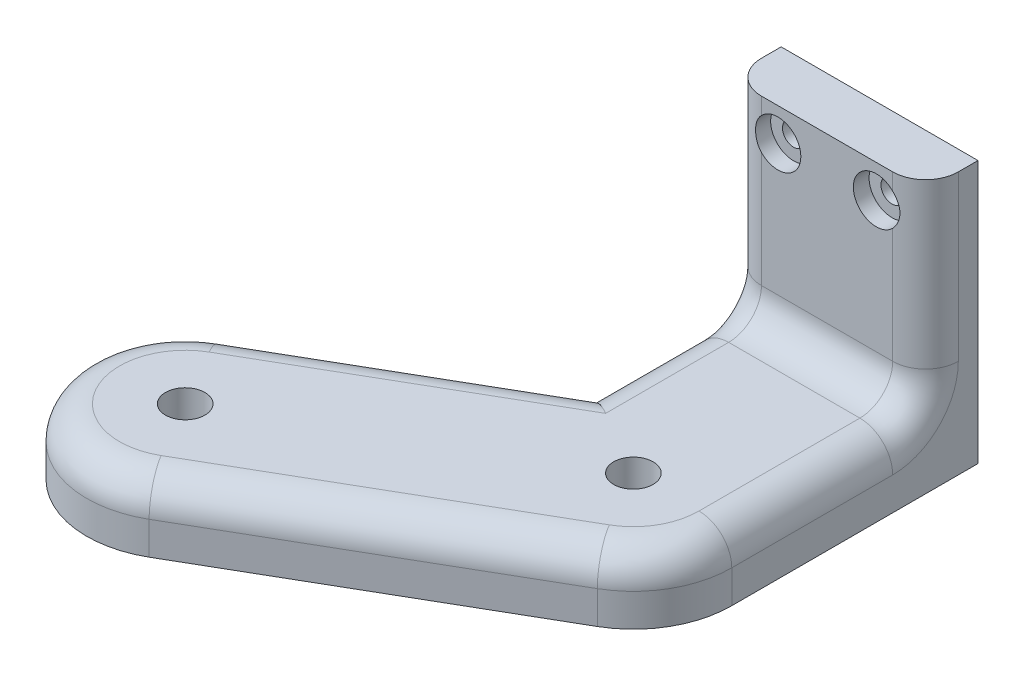
SolidWorks part; units mm, degrees
ref_plane "Alzado" through (0, 0, 0) normal (1, 0, 0) x (0, 1, 0)
ref_plane "Planta" through (0, 0, 0) normal (0, 0, 1) x (0, 1, 0)
ref_plane "Vista lateral" through (0, 0, 0) normal (0, 1, 0) x (-1, 0, 0)
sketch "Croquis1" plane through (0, 0, 0) normal (0, 1, 0) x (-1, 0, 0)
  line L0 (0, 37.5217) -> (43.3013, 62.5217) construction
  line L1 (15, 37.5217) -> (-15, 37.5217) construction
  line L2 (15, 37.5217) -> (15, 0) construction
  line L3 (15, 0) -> (-15, 0)
  line L4 (-15, 37.5217) -> (-15, 0)
  line L5 (15, 37.5217) -> (-15, 0) construction
  line L6 (15, 0) -> (-15, 37.5217) construction
  line L7 (-7.5, 50.5121) -> (35.8013, 75.5121)
  line L8 (15, 28.8614) -> (50.8013, 49.5313)
  line L9 (15, 0) -> (15, 28.8614)
  circle A0 centre (0, 37.5217) radius 3
  arc A1 (15, 37.5217) -> (-15, 37.5217) centre (0, 37.5217) ccw construction
  arc A2 (-7.5, 50.5121) -> (-15, 37.5217) centre (0, 37.5217) ccw
  arc A3 (50.8013, 49.5313) -> (35.8013, 75.5121) centre (43.3013, 62.5217) ccw
  circle A4 centre (43.3013, 62.5217) radius 3
  point P0 (0, 18.7609)
  point P9 (26.7532, 47.9677)
  dimension "D3" = 6
  dimension "D1" = 30
  dimension "D2" = 37.5217
  dimension "D4" = 30
  dimension "D5" = 50
extrude "Saliente-Extruir1" add sketch "Croquis1" along normal mid plane 10
sketch "Croquis2" plane through (0, 0, 0) normal (0, 0, -1) x (1, 0, 0)
  line L1 (15, -5) -> (-15, -5)
  line L2 (15, -5) -> (15, -35)
  line L3 (15, -35) -> (-15, -35)
  line L4 (-15, -5) -> (-15, -35)
  line L5 (-7.5, -30) -> (7.5, -30) construction
  line L6 (0, 0) -> (0, -30) construction
  line L7 (-15, -5) -> (-15, 5) construction
  point P7 (-7.5, -30)
  point P8 (7.5, -30)
  dimension "D1" = 30
  dimension "D2" = 30
  dimension "D3" = 15
extrude "Saliente-Extruir2" add sketch "Croquis2" against normal blind 8
sketch "Croquis6" plane through (0, 0, 8) normal (0, 0, 1) x (1, 0, 0)
  point P0 (-7.5, 30)
  point P1 (7.5, 30)
hole_wizard "Refrentado para tornillo con cabeza troncocónica de M31" positions "Croquis6" profile "Croquis7" counterbore size "M3" standard "Ansi Metric" end condition through all
sketch "Croquis7" plane through (-7.5, 30, 8) normal (1, 0, 0) x (0, -1, 0)
  line L0 (0, 0) -> (0, 8)
  line L1 (0, 8) -> (1.7, 8)
  line L3 (1.7, 8) -> (1.7, 2.4)
  line L4 (1.7, 2.4) -> (3.5, 2.4)
  line L5 (3.5, 2.4) -> (3.5, 0)
  line L7 (3.5, 0) -> (0, 0)
  line L11 (0, -6.35) -> (0, 107.95) construction
  dimension "Diámetro de taladro hasta el siguiente" = 3.4
  dimension "Profundidad de taladro hasta el siguiente" = 8
  dimension "Diámetro de refrentado" = 7
  dimension "Profundidad de refrentado" = 2.4
sketch "Croquis8" plane through (0, -5, 0) normal (0, -1, 0) x (1, 0, 0)
  circle A0 centre (0, 37.5217) radius 6.5
  dimension "D1" = 13
extrude "Cortar-Extruir1" [suppressed] cut sketch "Croquis8" against normal blind 5
ref_plane "Plano1" through (0, 5.5, 0) normal (0, 1, 0) x (1, 0, 0)
sketch "Croquis9" plane through (0, 5.5, 0) normal (0, 1, 0) x (1, 0, 0)
  line L0 (0, -37.5217) -> (-43.3013, -62.5217) construction
  line L1 (0, -37.5217) -> (-15, -37.5217) construction
  line L2 (0, -37.5217) -> (-43.3013, -62.5217) construction
  line L3 (4.0192, -52.5217) -> (-35.8013, -75.5121)
  line L5 (-50.8013, -49.5313) -> (-15, -28.8614)
  line L11 (-15, -28.8614) -> (-15, -37.5217)
  line L12 (4.0192, -52.5217) -> (0, -52.5217)
  line L13 (-35.8013, -75.5121) -> (7.5, -50.5121) construction
  arc A1 (-50.8013, -49.5313) -> (-35.8013, -75.5121) centre (-43.3013, -62.5217) ccw
  circle A3 centre (-43.3013, -62.5217) radius 3
  circle A4 centre (0, -37.5217) radius 3 construction
  circle A5 centre (0, -37.5217) radius 3 construction
  arc A8 (-50.8013, -49.5313) -> (-35.8013, -75.5121) centre (-43.3013, -62.5217) ccw construction
  arc A9 (-15, -37.5217) -> (0, -52.5217) centre (0, -37.5217) ccw
extrude "Saliente-Extruir3" [suppressed] add sketch "Croquis9" along normal blind 15 and the other way up to surface
mirror "Simetría1" [suppressed] about plane through (0, 5.5, 0) normal (0, 1, 0) of bodies 105
sketch "Croquis10" [suppressed] plane through (0, 5.5, 0) normal (0, 1, 0) x (1, 0, 0)
  line L0 (-45.5885, -40.7482) -> (-5.5885, -63.8422)
  line L1 (-20, -25.9747) -> (-53.3013, -45.2012) construction
  line L2 (-20, -25.9747) -> (-53.3013, -45.2012)
  line L3 (-33.3013, -79.8422) -> (5.359, -57.5217)
  line L4 (-45.5885, -40.7482) -> (-53.3013, -45.2012)
  line L5 (-33.3013, -79.8422) -> (-5.5885, -63.8422)
  line L6 (-33.3013, -79.8422) -> (5.359, -57.5217) construction
  line L8 (-20, -37.5217) -> (-20, -25.9747)
  line L17 (5.359, -57.5217) -> (0, -57.5217)
  arc A2 (-20, -37.5217) -> (0, -57.5217) centre (0, -37.5217) ccw
  arc A3 (-53.3013, -45.2012) -> (-33.3013, -79.8422) centre (-43.3013, -62.5217) ccw
  arc A5 (-53.3013, -45.2012) -> (-33.3013, -79.8422) centre (-43.3013, -62.5217) ccw
  dimension "D2" = 32
  dimension "D3" = 120
  dimension "D1" = 0
extrude "Cortar-Extruir2" [suppressed] cut sketch "Croquis10" against normal mid plane 10
sketch "Croquis11" plane through (0, -5, 0) normal (0, -1, 0) x (1, 0, 0)
  circle A0 centre (0, 37.5217) radius 6.5
  dimension "D1" = 13
extrude "Cortar-Extruir3" cut sketch "Croquis11" against normal blind 5
fillet "Redondeo4" [suppressed] radius 1
fillet "Redondeo6" [suppressed] radius 5
sketch "Croquis12" plane through (0, -5, 0) normal (0, -1, 0) x (1, 0, 0)
  line L0 (-90.9327, 90.0217) -> (-43.3013, 62.5217) construction
  line L1 (-83.4327, 103.0121) -> (-35.8013, 75.5121)
  line L2 (-98.4327, 77.0313) -> (-50.8013, 49.5313)
  line L3 (-43.3013, 62.5217) -> (0, 37.5217) construction
  line L4 (0, 37.5217) -> (0, 0) construction
  line L5 (15, 0) -> (-15, 0) construction
  arc A0 (-83.4327, 103.0121) -> (-98.4327, 77.0313) centre (-90.9327, 90.0217) ccw
  arc A1 (-50.8013, 49.5313) -> (-35.8013, 75.5121) centre (-43.3013, 62.5217) ccw
  arc A2 (-35.8013, 75.5121) -> (-50.8013, 49.5313) centre (-43.3013, 62.5217) ccw construction
  circle A3 centre (-90.9327, 90.0217) radius 3
  circle A4 centre (-43.3013, 62.5217) radius 3 construction
  circle A5 centre (-43.3013, 62.5217) radius 3
  point P3 (-67.117, 76.2717)
  dimension "D1" = 180
  dimension "D2" = 55
extrude "Saliente-Extruir4" [suppressed] add sketch "Croquis12" along normal blind 40 and the other way up to surface
ref_plane "Plano2" [suppressed] through (0, -23, 0) normal (0, -1, 0) x (-1, 0, 0)
sketch "Croquis13" [suppressed] plane through (0, -23, 0) normal (0, -1, 0) x (-1, 0, 0)
  line L0 (58.1369, -79.252) -> (40.4757, -83.9843)
  line L1 (100.9327, -72.7012) -> (44.0885, -39.8822) construction
  line L2 (5.0885, -63.5535) -> (80.9327, -107.3422) construction
  line L3 (65.208, -67.0046) -> (60.4757, -49.3433)
  line L4 (100.9327, -72.7012) -> (53.3013, -45.2012) construction
  line L5 (100.9327, -72.7012) -> (60.4757, -49.3433)
  line L6 (90.9327, -90.0217) -> (67.7962, -76.6638) construction
  line L8 (100.9327, -72.7012) -> (44.0885, -39.8822)
  line L10 (5.0885, -63.5535) -> (80.9327, -107.3422)
  line L12 (44.0885, -41.6142) -> (6.0885, -63.5535)
  line L15 (40.4757, -83.9843) -> (80.9327, -107.3422)
  arc A0 (33.3013, -79.8422) -> (53.3013, -45.2012) centre (43.3013, -62.5217) ccw construction
  arc A1 (65.208, -67.0046) -> (58.1369, -79.252) centre (55.5487, -69.5928) cw
  arc A5 (80.9327, -107.3422) -> (100.9327, -72.7012) centre (90.9327, -90.0217) ccw
  arc A6 (5.0885, -63.5535) -> (6.0885, -63.5535) centre (5.5885, -62.6875) ccw
  arc A7 (44.0885, -41.6142) -> (44.0885, -39.8822) centre (43.5885, -40.7482) ccw
  arc A9 (80.9327, -107.3422) -> (100.9327, -72.7012) centre (90.9327, -90.0217) ccw
  arc A10 (5.0885, -63.5535) -> (6.0885, -63.5535) centre (5.5885, -62.6875) ccw
  dimension "D2" = 10
  dimension "D3" = 45
  dimension "D1" = 0
extrude "Cortar-Extruir4" [suppressed] cut sketch "Croquis13" against normal mid plane 30 contours L0 L15 A9 L5 L3 A1
sketch "Croquis14" [suppressed] plane through (0, -45, 0) normal (0, -1, 0) x (1, 0, 0)
  line L1 (-40.4757, 83.9843) -> (-80.9327, 107.3422) construction
  line L2 (-100.9327, 72.7012) -> (-53.3013, 45.2012)
  line L3 (-33.3013, 79.8422) -> (-80.9327, 107.3422)
  line L4 (-57.6314, 47.7012) -> (-53.3013, 45.2012)
  line L6 (-40.4757, 83.9843) -> (-80.9327, 107.3422) construction
  line L7 (-100.9327, 72.7012) -> (-53.3013, 45.2012) construction
  line L8 (-33.3013, 79.8422) -> (-37.6314, 82.3422)
  line L9 (-33.3013, 79.8422) -> (-80.9327, 107.3422) construction
  line L10 (-37.6314, 82.3422) -> (-57.6314, 47.7012)
  arc A2 (-80.9327, 107.3422) -> (-100.9327, 72.7012) centre (-90.9327, 90.0217) ccw
  arc A3 (-53.3013, 45.2012) -> (-33.3013, 79.8422) centre (-43.3013, 62.5217) ccw
  arc A5 (-53.3013, 45.2012) -> (-33.3013, 79.8422) centre (-43.3013, 62.5217) ccw
  dimension "D2" = 5
  dimension "D1" = 0
extrude "Cortar-Extruir5" [suppressed] cut sketch "Croquis14" against normal up to surface (40 mm away)
fillet "Redondeo7" [suppressed] radius 5
fillet "Redondeo8" radius 5 9 edges at (15, 20, 8) (-15, 20, 8) (-32.9006, 5, 39.1964) (-56.2917, 5, 70.0217) (-14.1506, 5, 63.0121) (15, 5, 22.7608) (0, 5, 8) (-15, 5, 18.4307) (12.9904, 5, 45.0217)
equation "\"ancho\"=30"
equation "\"D1@Croquis1\"=\"ancho\""
equation "\"distancia-eje-polea\"= 17.5217 + 20"
equation "\"D2@Croquis1\"=\"distancia-eje-polea\""
equation "\"agujero\"= 6"
equation "\"D3@Croquis1\"=\"agujero\""
equation "\"esp\"=10"
equation "\"D1@Saliente-Extruir1\"=\"esp\""
equation "\"D2@Croquis2\"=\"esp\"*3"
equation "\"D1@Croquis2\"=\"esp\"*3"
equation "\"D3@Croquis2\"=\"ancho\"/2"
equation "\"d_rodamiento\"= 13"
equation "\"D1@Croquis8\"=\"d_rodamiento\""
equation "\"a_rodamiento\"=5"
equation "\"D1@Cortar-Extruir1\"=\"a_rodamiento\""
equation "\"angulo\"=30"
equation "\"Zbarra\"=50"
equation "\"D1@Croquis11\"=\"d_rodamiento\""
equation "\"D4@Croquis1\"=\"angulo\""
equation "\"D5@Croquis1\"=\"Zbarra\""
